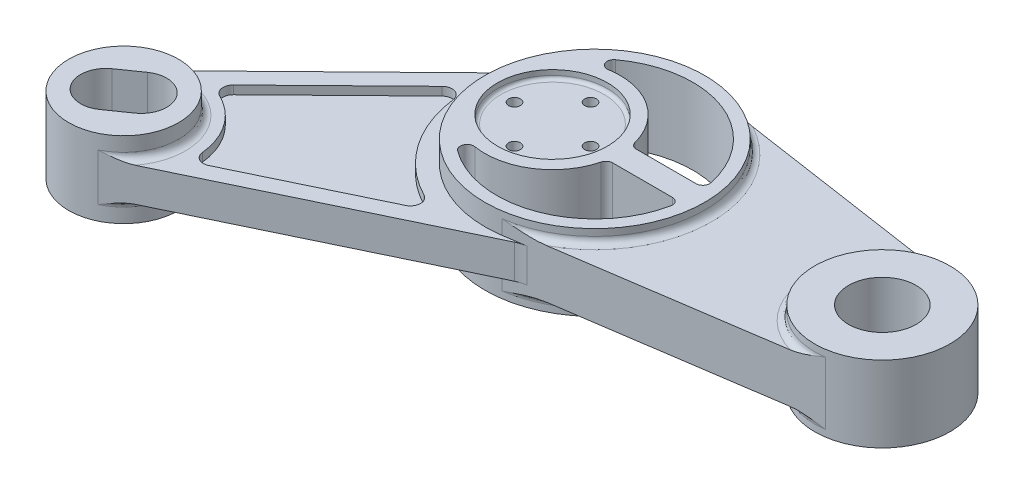
SolidWorks part; units mm, degrees
ref_plane "Piano frontale" through (0, 0, 0) normal (0, 0, 1) x (1, 0, 0)
ref_plane "Piano superiore" through (0, 0, 0) normal (0, 1, 0) x (1, 0, 0)
ref_plane "Piano destro" through (0, 0, 0) normal (1, 0, 0) x (0, 0, -1)
sketch "Schizzo1" plane through (0, 0, 0) normal (0, 1, 0) x (1, 0, 0)
  line L0 (0, 0) -> (250, 0) construction
  line L1 (0, 0) -> (-204.788, -143.3941) construction
  line L2 (0, 0) -> (0, 250) construction
  line L3 (9.5588, 64.2933) -> (175.8824, 39.5651)
  line L4 (-45.4392, 46.4788) -> (-186.55, -91.4759)
  line L5 (-149.7631, -144.0131) -> (28.1346, -58.5956) construction
  line L6 (175.8824, -39.5651) -> (9.5588, -64.2933)
  line L7 (-149.7631, -144.0131) -> (19.2774, -62.8484)
  circle A0 centre (170, 0) radius 40
  circle A1 centre (-163.8304, -114.7153) radius 32.5
  circle A2 centre (0, 0) radius 65
  dimension "D3" = 130
  dimension "D4" = 80
  dimension "D5" = 65
  dimension "D1" = 125
  dimension "D2" = 200
  dimension "D6" = 170
extrude "Estrusione-Estrusione1" add sketch "Schizzo1" along normal mid plane 45 contours A2 | A0 | A1 region at (0, 0, 0) region at (170, 0, 0) region at (-163.8304, 0, 114.7153)
extrude "Estrusione-Estrusione2" add sketch "Schizzo1<4>" along normal mid plane 20 contours L5 L6 A2 L4 A1 region at (-90.4456, 0, 63.299)
sketch "Schizzo1<4>" plane through (0, 0, 0) normal (0, 1, 0) x (1, 0, 0) same geometry as "Schizzo1"
extrude "Estrusione-Estrusione5" add sketch "Schizzo1<7>" along normal mid plane 29 contours A2 L6 A0 L3 region at (94.9909, 0, 0)
sketch "Schizzo1<7>" plane through (0, 0, 0) normal (0, 1, 0) x (1, 0, 0) same geometry as "Schizzo1"
sketch "Schizzo2" plane through (0, 22.5, 0) normal (0, 1, 0) x (1, 0, 0)
  line L0 (-182.4716, -88.0928) -> (-145.1892, -141.3377) construction
  line L1 (-163.8304, -114.7153) -> (0, 0) construction
  line L2 (-157.6868, -110.4135) -> (-169.974, -119.0171) construction
  line L3 (-149.0831, -122.7007) -> (-161.3704, -131.3044)
  line L4 (-166.2904, -98.1262) -> (-178.5777, -106.7298)
  circle A0 centre (170, 0) radius 20
  circle A1 centre (-163.8304, -114.7153) radius 32.5 construction
  arc A2 (-149.0831, -122.7007) -> (-166.2904, -98.1262) centre (-157.6868, -110.4135) ccw
  arc A3 (-178.5777, -106.7298) -> (-161.3704, -131.3044) centre (-169.974, -119.0171) ccw
  point P9 (-163.8304, -114.7153)
  dimension "D1" = 40
  dimension "D4" = 15
  dimension "D2" = 65
  dimension "D3" = 7.5
extrude "Taglio-Estrusione1" cut sketch "Schizzo2" against normal through all
sketch "Schizzo3" plane through (0, 22.5, 0) normal (0, 1, 0) x (1, 0, 0)
  line L0 (0, 0) -> (170, 0) construction
  line L1 (14.3827, -7) -> (57.576, -7)
  line L2 (14.3827, 7) -> (57.576, 7)
  arc A0 (-47.78, -32.8797) -> (57.576, -7) centre (0, 0) ccw
  arc A2 (-47.78, -32.8797) -> (14.3827, -7) centre (-25, 0) ccw
  arc A3 (14.3827, 7) -> (-47.78, 32.8797) centre (-25, 0) ccw
  arc A4 (57.576, 7) -> (-47.78, 32.8797) centre (0, 0) ccw
  dimension "D1" = 116
  dimension "D2" = 80
  dimension "D3" = 25
  dimension "D4" = 14
extrude "Taglio-Estrusione2" cut sketch "Schizzo3" against normal through all
sketch "Schizzo4" plane through (0, 10, 0) normal (0, 1, 0) x (1, 0, 0)
  line L0 (-163.8304, -114.7153) -> (0, 0) construction
  line L1 (-153.7776, -73.4213) -> (-74.9095, 3.6827)
  line L2 (-121.5885, -119.3921) -> (-22.1599, -71.6515)
  line L3 (-45.4392, 46.4788) -> (-186.55, -91.4759) construction
  line L4 (-149.7631, -144.0131) -> (19.2774, -62.8484) construction
  arc A0 (-121.5885, -119.3921) -> (-153.7776, -73.4213) centre (-163.8304, -114.7153) ccw
  arc A1 (-74.9095, 3.6827) -> (-22.1599, -71.6515) centre (0, 0) ccw
  dimension "D1" = 150
  dimension "D2" = 85
  dimension "D3" = 10
  dimension "D4" = 10
extrude "Taglio-Estrusione3" cut sketch "Schizzo4" against normal blind 5
sketch "Schizzo5" plane through (0, 22.5, 0) normal (0, 1, 0) x (1, 0, 0)
  circle A0 centre (-25, 0) radius 32.5
  dimension "D1" = 65
extrude "Taglio-Estrusione4" cut sketch "Schizzo5" against normal blind 5
mirror "Specchia2" about plane through (0, 0, 0) normal (0, 1, 0) of "Taglio-Estrusione4", "Taglio-Estrusione3"
hole_wizard "Foro filettato M8x1.0-1" positions "Schizzo6" profile "Schizzo7" tap size "M8x1.0" standard "ISO" end condition through all
sketch "Schizzo6" plane through (0, 17.5, 0) normal (0, 1, 0) x (1, 0, 0)
  point P0 (-25, 22.5)
  dimension "D1" = 22.5
cosmetic thread "Filettatura del foro1" parameters "D2"=8
sketch "Schizzo7" plane through (-25, 17.5, -22.5) normal (1, 0, 0) x (0, 0, 1)
  line L0 (0, 0) -> (0, 40)
  line L1 (0, 40) -> (3.5, 40)
  line L2 (3.5, 40) -> (3.5, 0)
  line L5 (3.5, 0) -> (0, 0)
  line L11 (0, -6.35) -> (0, 107.95) construction
  dimension "Thru Tap Drill Dia." = 7
  dimension "Thru Tap Drill Depth" = 40
pattern_circular "RipetizioneCircolare1" count 4 every 90 about axis through (-25, -22.5, 0) along (0, 1, 0) of "Foro filettato M8x1.0-1"
cosmetic thread "Filettatura del foro2" parameters "D2"=8
cosmetic thread "Filettatura del foro3" parameters "D2"=8
cosmetic thread "Filettatura del foro4" parameters "D2"=8
fillet "Raccordo1" radius 4 12 edges at (-137.208, -10, 96.0741) (-137.208, 10, 96.0741) (130, -14.5, 0) (65, -14.5, 0) (130, 14.5, 0) (65, 14.5, 0) (-47.78, 0, -32.8797) (57.576, 0, -7) (14.3827, 0, -7) (-47.78, 0, 32.8797) (57.576, 0, 7) (14.3827, 0, 7)
fillet "Raccordo2" radius 20 1 edges at (19.2774, 0, 62.8484)
fillet "Raccordo3" radius 6 8 edges at (-74.9095, -7.5, -3.6827) (-121.5885, -7.5, 119.3921) (-22.1599, -7.5, 71.6515) (-153.7776, -7.5, 73.4213) (-22.1599, 7.5, 71.6515) (-74.9095, 7.5, -3.6827) (-153.7776, 7.5, 73.4213) (-121.5885, 7.5, 119.3921)
fillet "Raccordo4" radius 2 2 edges at (-25, -17.5, 32.5) (-25, 17.5, 32.5)
